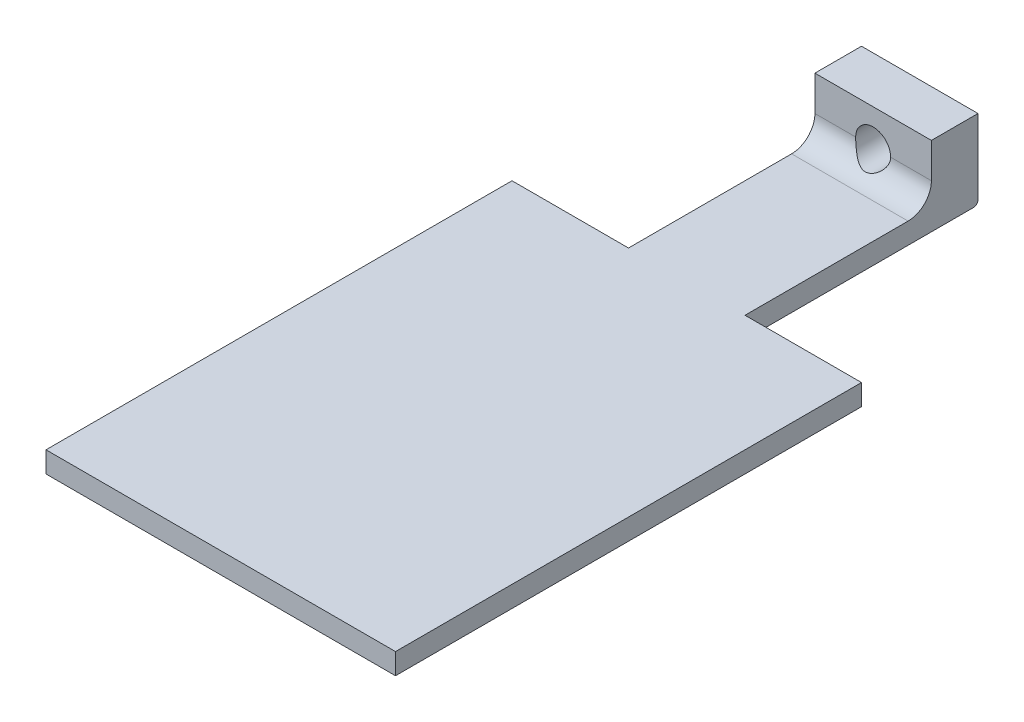
SolidWorks part; units mm, degrees
ref_plane "Front Plane" through (0, 0, 0) normal (0, 0, 1) x (1, 0, 0)
ref_plane "Top Plane" through (0, 0, 0) normal (0, 1, 0) x (1, 0, 0)
ref_plane "Right Plane" through (0, 0, 0) normal (1, 0, 0) x (0, 0, -1)
sketch "Sketch1" plane through (0, 0, 0) normal (0, 1, 0) x (1, 0, 0)
  line L0 (20, 0) -> (30, 0)
  line L1 (0, 0) -> (10, 0)
  line L2 (0, 0) -> (0, -40)
  line L3 (0, -40) -> (30, -40)
  line L4 (30, 0) -> (30, -40)
  line L6 (10, 0) -> (10, 20)
  line L7 (10, 20) -> (20, 20)
  line L8 (20, 0) -> (20, 20)
  dimension "D1" = 30
  dimension "D2" = 40
  dimension "D3" = 10
  dimension "D5" = 20
extrude "Boss-Extrude1" add sketch "Sketch1" along normal blind 1.8
sketch "Sketch2" plane through (0, 1.8, 0) normal (0, 1, 0) x (1, 0, 0)
  line L0 (20, 0) -> (20, 20) construction
  line L1 (10, 20) -> (20, 20)
  line L2 (10, 20) -> (10, 16)
  line L3 (10, 16) -> (20, 16)
  line L4 (20, 20) -> (20, 16)
  dimension "D1" = 4
extrude "Boss-Extrude2" add sketch "Sketch2" along normal blind 5
sketch "Sketch3" plane through (0, 0, -20) normal (0, 0, -1) x (-1, 0, 0)
  line L0 (-20, 6.8) -> (-10, 6.8) construction
  circle A0 centre (-15, 3.8) radius 1.5
  point P4 (-15, 6.8)
  dimension "D1" = 3
  dimension "D2" = 0
  dimension "D3" = 3
extrude "Cut-Extrude1" cut sketch "Sketch3" against normal blind 5
fillet "Fillet1" radius 2 1 edges at (15, 1.8, -16)
fillet "Fillet2" radius 0.4 1 edges at (15, 0, -20)
